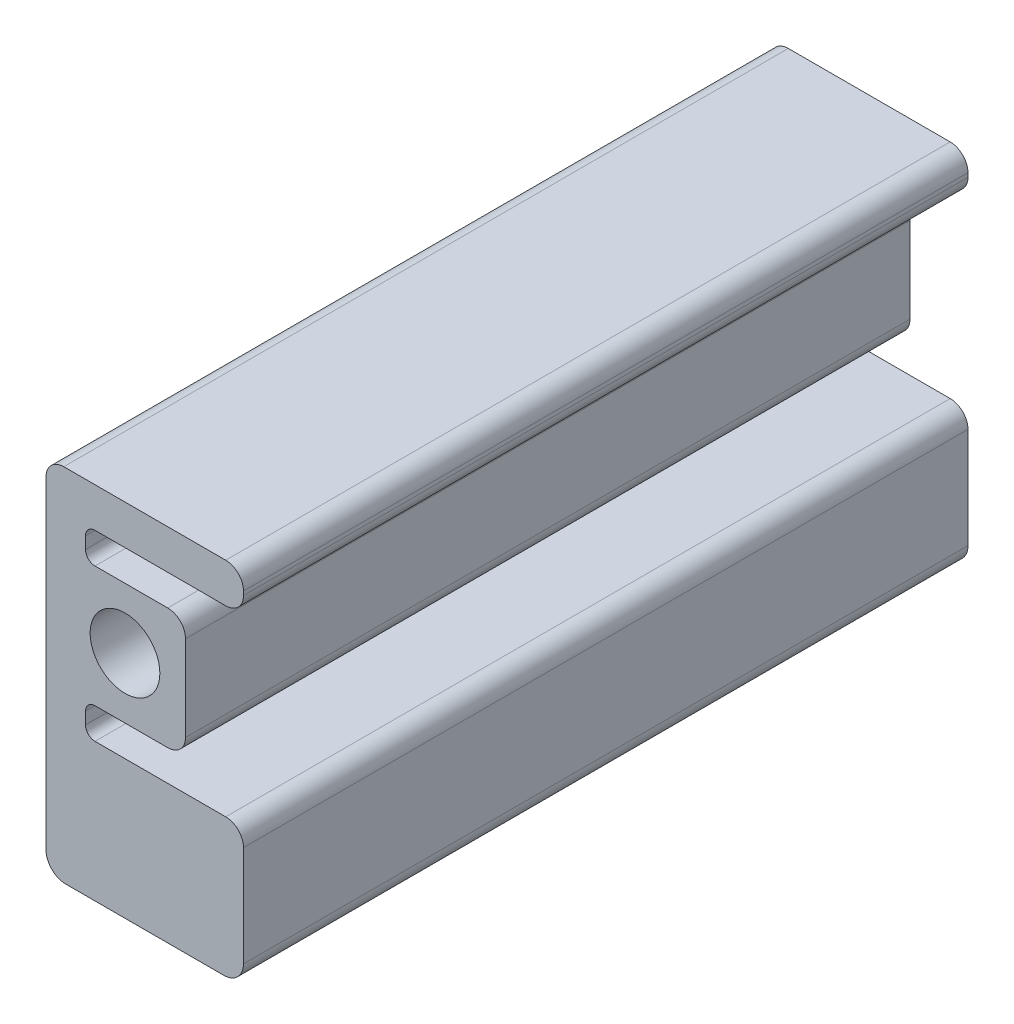
SolidWorks part; units mm, degrees
material "Pink Foam"
ref_plane "Front Plane" through (0, 0, 0) normal (0, 0, 1) x (1, 0, 0)
ref_plane "Top Plane" through (0, 0, 0) normal (0, 1, 0) x (1, 0, 0)
ref_plane "Right Plane" through (0, 0, 0) normal (1, 0, 0) x (0, 0, -1)
sketch "Sketch1" plane through (0, 0, 0) normal (0, 0, 1) x (1, 0, 0)
  line L0 (-25.4, -67.48) -> (-25.4, 36.365)
  line L2 (38.1, -67.48) -> (38.1, -35.095)
  line L3 (32.385, -29.38) -> (-9.652, -29.38)
  line L4 (-12.7, -26.332) -> (-12.7, -22.503)
  line L5 (-9.652, -19.455) -> (0, -19.455)
  line L6 (-9.652, 19.455) -> (0, 19.455)
  line L7 (-12.7, 22.503) -> (-12.7, 26.332)
  line L8 (-9.652, 29.38) -> (32.385, 29.38)
  line L9 (38.1, 35.095) -> (38.1, 36.365)
  line L10 (32.385, 42.08) -> (-19.685, 42.08)
  line L15 (0, -11.2) -> (0, -19.455) construction
  line L16 (0, 11.2) -> (0, 19.455) construction
  line L17 (11.2, 0) -> (19.455, 0) construction
  line L18 (0, 19.455) -> (13.74, 19.455)
  line L19 (19.455, 13.74) -> (19.455, 0)
  line L20 (19.455, 0) -> (19.455, -13.74)
  line L21 (13.74, -19.455) -> (0, -19.455)
  line L24 (31.75, -73.83) -> (-19.05, -73.83)
  circle A0 centre (0, 0) radius 11.2
  arc A3 (-19.685, 42.08) -> (-25.4, 36.365) centre (-19.685, 36.365) ccw
  arc A4 (38.1, 36.365) -> (32.385, 42.08) centre (32.385, 36.365) ccw
  arc A6 (32.385, 29.38) -> (38.1, 35.095) centre (32.385, 35.095) ccw
  arc A7 (38.1, -35.095) -> (32.385, -29.38) centre (32.385, -35.095) ccw
  arc A8 (19.455, -13.74) -> (13.74, -19.455) centre (13.74, -13.74) cw
  arc A9 (13.74, 19.455) -> (19.455, 13.74) centre (13.74, 13.74) cw
  arc A10 (-12.7, 26.332) -> (-9.652, 29.38) centre (-9.652, 26.332) cw
  arc A11 (-9.652, 19.455) -> (-12.7, 22.503) centre (-9.652, 22.503) cw
  arc A12 (-12.7, -22.503) -> (-9.652, -19.455) centre (-9.652, -22.503) cw
  arc A13 (-9.652, -29.38) -> (-12.7, -26.332) centre (-9.652, -26.332) cw
  arc A14 (31.75, -73.83) -> (38.1, -67.48) centre (31.75, -67.48) ccw
  arc A15 (-19.05, -73.83) -> (-25.4, -67.48) centre (-19.05, -67.48) cw
  point P12 (0, 11.2)
  point P20 (0, -11.2)
  point P22 (11.2, 0)
  point P45 (-12.7, 29.38)
  point P48 (-12.7, 19.455)
  point P53 (-12.7, -29.38)
  point P57 (38.1, -73.83)
  point P60 (38.1, -73.83)
  point P63 (-25.4, -73.83)
  dimension "D1" = 22.4
  dimension "D11" = 3.048
  dimension "D9" = 5.715
  dimension "D14" = 5.715
  dimension "D12" = 6.35
  dimension "D2" = 25.4
  dimension "D3" = 8.255
  dimension "D4" = 9.925
  dimension "D5" = 44.45
  dimension "D6" = 9.925
  dimension "D7" = 12.7
  dimension "D8" = 12.7
  dimension "D10" = 63.5
extrude "Boss-Extrude1" add sketch "Sketch1" along normal blind 232.9473
